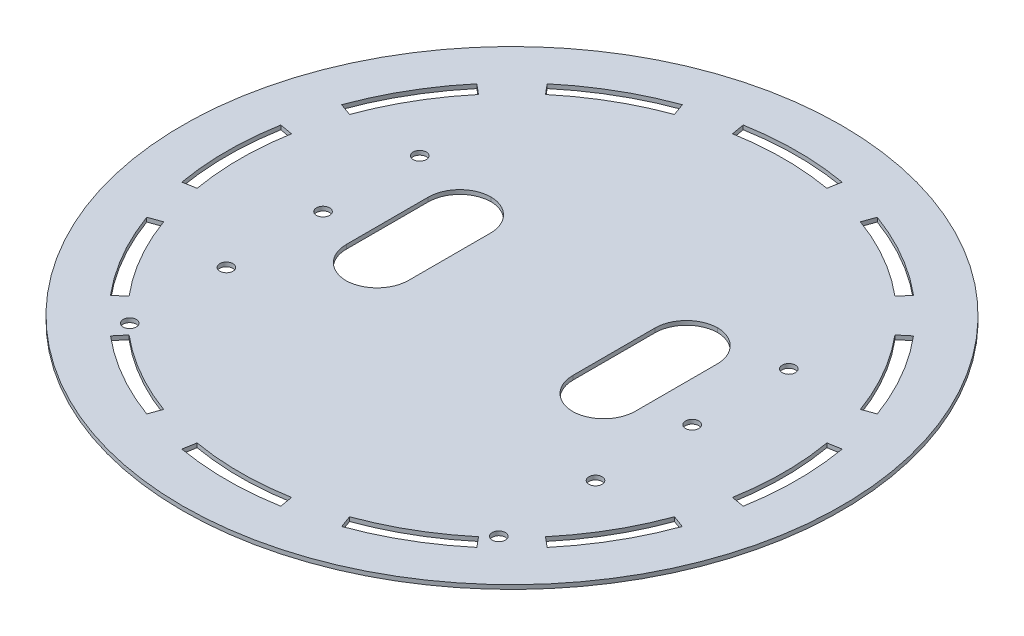
SolidWorks part; units mm, degrees
ref_plane "Front Plane" through (0, 0, 0) normal (0, 0, 1) x (1, 0, 0)
ref_plane "Top Plane" through (0, 0, 0) normal (0, 1, 0) x (1, 0, 0)
ref_plane "Right Plane" through (0, 0, 0) normal (1, 0, 0) x (0, 0, -1)
sketch "Sketch1" plane through (0, 0, 0) normal (0, 1, 0) x (1, 0, 0)
  line L0 (0, 0) -> (0, -79.375)
  line L1 (7.1438, -66.675) -> (-7.1437, -66.675)
  line L2 (50.8, 22.225) -> (76.2, 22.225)
  line L3 (-63.5, -47.625) -> (-50.8, -47.625)
  line L4 (-50.8, -47.625) -> (-50.8, 22.225)
  line L5 (63.5, -47.625) -> (50.8, -47.625)
  line L6 (50.8, -47.625) -> (50.8, 22.225)
  line L7 (-50.8, 22.225) -> (-76.2, 22.225)
  line L8 (0, 0) -> (-27.2811, 0)
  circle A0 centre (0, 0) radius 79.375
  circle A1 centre (-7.1437, -66.675) radius 1.5875
  circle A2 centre (7.1438, -66.675) radius 1.5875
  circle A3 centre (7.1438, 66.675) radius 1.5875
  circle A4 centre (-7.1437, 66.675) radius 1.5875
  point P7 (0, -66.675)
  dimension "D1" = 7.1437
  dimension "D3" = 50.8
  dimension "D6" = 3.175
  dimension "D2" = 12.7
  dimension "D4" = 69.85
  dimension "D5" = 47.625
extrude "Boss-Extrude5" add sketch "Sketch1" along normal blind 1.5875 contours A2 A0 L5 L6 L2 L7 L4 L3 A1 A3 region at (0, 0, -2.0947)
fillet "Fillet2" radius 2.54 1 edges at (-63.5, 0.7937, 47.625)
fillet "Fillet3" radius 2.54 1 edges at (63.5, 0.7937, 47.625)
fillet "Fillet4" radius 5.08 2 edges at (-76.2, 0.7937, -22.225) (76.2, 0.7937, -22.225)
sketch "Sketch2" plane through (0, 1.5875, 0) normal (0, 1, 0) x (1, 0, 0)
  line L0 (0, 0) -> (0, 79.375)
  line L1 (0, 0) -> (-67.0566, 0)
  line L2 (0, 0) -> (-61.0886, 27.6545)
  line L3 (0, 0) -> (-43.6778, 50.8806)
  line L4 (0, 0) -> (-63.2664, 22.225)
  line L5 (-50.8, 22.225) -> (-69.0955, 22.225) construction
  line L6 (0, 0) -> (0, 2.6153)
  line L7 (0, 0) -> (-39.0771, 54.4938)
  line L8 (0, 0) -> (-12.3858, 65.9028)
  line L9 (-62.5348, 28.3092) -> (-59.6424, 26.9998)
  line L10 (-43.6778, 50.8806) -> (-44.7118, 52.0852)
  line L11 (-43.6778, 50.8806) -> (-42.6438, 49.6761)
  line L12 (-39.0771, 54.4938) -> (-40.0022, 55.7839)
  line L13 (-39.0771, 54.4938) -> (-38.152, 53.2037)
  line L14 (-43.6778, 50.8806) -> (-42.6438, 49.6761)
  line L15 (-12.3858, 65.9028) -> (-12.0926, 64.3426)
  line L16 (-12.3858, 65.9028) -> (-12.679, 67.463)
  line L17 (61.5813, 22.225) -> (64.9466, 22.225)
  line L18 (50.8, 22.225) -> (69.0955, 22.225) construction
  line L19 (12.3858, 65.9028) -> (12.679, 67.463)
  line L20 (12.3858, 65.9028) -> (12.0926, 64.3426)
  line L21 (39.0771, 54.4938) -> (38.152, 53.2037)
  line L22 (43.6778, 50.8806) -> (42.6438, 49.6761)
  line L23 (39.0771, 54.4938) -> (40.0022, 55.7839)
  line L24 (43.6778, 50.8806) -> (42.6438, 49.6761)
  line L25 (43.6778, 50.8806) -> (44.7118, 52.0852)
  line L26 (62.5348, 28.3092) -> (59.6424, 26.9998)
  line L27 (-50.8, -41.2985) -> (-50.8, -43.7716)
  line L28 (-50.8, -47.625) -> (-50.8, 22.225) construction
  line L29 (50.8, -41.2985) -> (50.8, -46.1668)
  line L30 (50.8, -47.625) -> (50.8, 22.225) construction
  line L31 (39.0771, -54.4938) -> (40.0022, -55.7839)
  line L32 (39.0771, -54.4938) -> (38.152, -53.2037)
  line L33 (12.3858, -65.9028) -> (12.0926, -64.3426)
  line L34 (12.3858, -65.9028) -> (12.679, -67.463)
  line L35 (-12.3858, -65.9028) -> (-12.679, -67.463)
  line L36 (-12.3858, -65.9028) -> (-12.0926, -64.3426)
  line L37 (-39.0771, -54.4938) -> (-38.152, -53.2037)
  line L38 (-39.0771, -54.4938) -> (-40.0022, -55.7839)
  arc A0 (-63.2664, 22.225) -> (-50.8, -43.7716) centre (0, 0) ccw
  arc A1 (73.8199, 29.172) -> (-73.8199, 29.172) centre (0, 0) ccw construction
  circle A2 centre (-7.1437, 66.675) radius 2.3813
  circle A3 centre (7.1437, 66.675) radius 2.3813
  circle A4 centre (7.1437, -66.675) radius 2.3813
  circle A5 centre (-7.1437, -66.675) radius 2.3813
  arc A6 (12.679, -67.463) -> (40.0022, -55.7839) centre (0, 0) ccw
  arc A7 (-61.7686, 21.6988) -> (-50.8, -41.2985) centre (0, 0) ccw
  arc A8 (-44.7118, 52.0852) -> (-62.5348, 28.3092) centre (0, 0) ccw
  arc A9 (-42.6438, 49.6761) -> (-59.6424, 26.9998) centre (0, 0) ccw
  arc A10 (12.0926, 64.3426) -> (38.152, 53.2037) centre (0, 0) cw
  arc A11 (12.679, 67.463) -> (40.0022, 55.7839) centre (0, 0) cw
  arc A12 (42.6438, 49.6761) -> (59.6424, 26.9998) centre (0, 0) cw
  arc A13 (-12.679, 67.463) -> (-40.0022, 55.7839) centre (0, 0) ccw
  arc A14 (44.7118, 52.0852) -> (62.5348, 28.3092) centre (0, 0) cw
  arc A15 (-12.0926, 64.3426) -> (-38.152, 53.2037) centre (0, 0) ccw
  arc A16 (12.0926, -64.3426) -> (38.152, -53.2037) centre (0, 0) ccw
  arc A17 (-12.0926, -64.3426) -> (-38.152, -53.2037) centre (0, 0) cw
  arc A18 (50.8, -46.1668) -> (64.9466, 22.225) centre (0, 0) ccw
  arc A19 (50.8, -43.7716) -> (63.2664, 22.225) centre (0, 0) ccw
  arc A20 (50.8, -41.2985) -> (61.5813, 22.225) centre (0, 0) ccw
  arc A21 (-12.679, -67.463) -> (-40.0022, -55.7839) centre (0, 0) cw
  circle M13 centre (-7.1437, -66.675) radius 1.5875
  circle M14 centre (7.1438, -66.675) radius 1.5875
  circle M15 centre (7.1438, 66.675) radius 1.5875
  circle M16 centre (-7.1437, 66.675) radius 1.5875
  dimension "D2" = 4.7625
  dimension "D7" = 1.5875
  dimension "D8" = 3.175
  dimension "D1" = 5
  dimension "D3" = 25
  dimension "D4" = 5
  dimension "D5" = 25
extrude "Cut-Extrude1" cut sketch "Sketch2" against normal blind 2.54 contours A9 L3 L10 A8 L9 L2 | A15 L8 L16 A13 L12 L7 | A2 M16 | A3 M15 | A11 L19 L20 A10 L21 L23 | A14 L25 L22 A12 L26 | A21 L35 L36 A17 L37 L38 | A5 M13 | A4 M14 | A16 L33 L34 A6 L31 L32 region at (-53.2404, 1.5875, -39.9101) region at (-26.1525, 1.5875, -61.1833) region at (26.1525, 1.5875, -61.1833) region at (53.2404, 1.5875, -39.9101) region at (26.1525, 1.5875, 61.1833) region at (-26.1525, 1.5875, 61.1833) region at (-9.4576, 1.5875, -66.675) region at (4.8299, 1.5875, -66.675) region at (4.8299, 1.5875, 66.675) region at (-9.4576, 1.5875, 66.675)
sketch "Sketch3" plane through (0, 1.5875, 0) normal (0, 1, 0) x (1, 0, 0)
  line L0 (-50.8, 22.225) -> (-50.8, -47.625)
  line L1 (-50.8, -47.625) -> (-44.45, -47.625)
  line L2 (-50.8, 22.225) -> (-44.45, 22.225)
  line L3 (0, 0) -> (0, 32.9013)
  circle A0 centre (-44.45, -47.625) radius 1.5875
  circle A1 centre (-44.45, 22.225) radius 1.5875
  circle A2 centre (44.45, 22.225) radius 1.5875
  circle A3 centre (44.45, -47.625) radius 1.5875
  dimension "D2" = 3.175
  dimension "D4" = 3.175
  dimension "D1" = 6.35
  dimension "D3" = 6.35
extrude "Cut-Extrude2" cut sketch "Sketch3" against normal blind 2.54 contours A1 | A2 | A0 | A3 region at (-44.45, 1.5875, 46.0824) region at (-44.45, 1.5875, -23.7676) region at (44.45, 1.5875, -22.225) region at (44.45, 1.5875, 47.625)
sketch "Sketch4" plane through (0, 1.5875, 0) normal (0, 1, 0) x (1, 0, 0)
  line L0 (-44.45, -47.625) -> (-44.45, 22.225)
  line L1 (-44.45, 22.225) -> (-50.8, 22.225)
  line L2 (-50.8, -47.625) -> (-50.8, 22.225) construction
  line L3 (0, 0) -> (0, -67.5878)
  line L4 (44.45, -47.625) -> (44.45, 22.225)
  circle A0 centre (-44.45, 22.225) radius 1.5875
  circle A1 centre (-44.45, -12.7) radius 1.5875
  circle A2 centre (44.45, -12.7) radius 1.5875
  dimension "D2" = 3.175
  dimension "D1" = 69.85
extrude "Cut-Extrude3" cut sketch "Sketch4" against normal blind 2.54 contours L0 A1 | L0 A1 | A2 L4 | A2 L4 region at (-45.1238, 1.5875, 12.7) region at (-43.7762, 1.5875, 12.7) region at (43.7762, 1.5875, 12.7) region at (45.1238, 1.5875, 12.7)
sketch "Sketch5" plane through (0, 1.5875, 0) normal (0, 1, 0) x (1, 0, 0)
  line L0 (-50.8, -12.7) -> (-34.8, -12.7)
  line L1 (-50.8, -47.625) -> (-50.8, 22.225) construction
  line L2 (-50.8, 22.225) -> (-34.8, 22.225)
  line L3 (-34.8, 22.225) -> (-34.8, -12.7)
  line L4 (0, 0) -> (0, 64.5379)
  line L5 (-34.8, 22.225) -> (-19.8, 22.225)
  line L6 (-19.8, 22.225) -> (-19.8, -12.7)
  line L7 (-19.8, -12.7) -> (-34.8, -12.7)
  line L8 (19.8, -12.7) -> (34.8, -12.7)
  line L9 (19.8, 22.225) -> (19.8, -12.7)
  line L10 (34.8, 22.225) -> (19.8, 22.225)
  line L11 (34.8, 22.225) -> (34.8, -12.7)
  dimension "D1" = 16
  dimension "D2" = 16
extrude "Cut-Extrude4" cut sketch "Sketch5" against normal through all contours L7 L6 L5 L3 | L11 L10 L9 L8 region at (-27.3, 1.5875, -4.7625) region at (27.3, 1.5875, -4.7625)
fillet "Fillet5" radius 7.62 4 edges at (-19.8, 0.7937, 12.7) (-34.8, 0.7937, 12.7) (-19.8, 0.7937, -22.225) (-34.8, 0.7937, -22.225)
fillet "Fillet6" radius 7.62 4 edges at (34.8, 0.7937, 12.7) (34.8, 0.7937, -22.225) (19.8, 0.7937, -22.225) (19.8, 0.7937, 12.7)
sketch "Sketch6" plane through (0, 1.5875, 0) normal (0, 1, 0) x (1, 0, 0)
  line L0 (-50.8, 22.225) -> (-69.0955, 22.225)
  line L1 (-69.0955, 22.225) -> (-69.0955, 39.0667)
  line L2 (-50.8, 22.225) -> (-50.8, -60.9898)
  line L3 (50.8, 22.225) -> (69.0955, 22.225)
  line L4 (69.0955, 22.225) -> (69.0955, 39.0667)
  line L5 (50.8, 22.225) -> (50.8, -60.9898)
  circle A0 centre (0, 0) radius 79.375
extrude "Boss-Extrude6" add sketch "Sketch6" against normal blind 1.5875 contours L1 A0 L2 L0 | L5 A0 L4 L3 region at (-63.4454, 1.5875, 10.5781) region at (63.4454, 1.5875, 10.5781)
sketch "Sketch7" plane through (0, 0, 0) normal (0, -1, 0) x (1, 0, 0)
  circle A0 centre (0, 0) radius 79.375
extrude "Cut-Extrude5" cut sketch "Sketch7" against normal blind 0.5875
sketch "Sketch8" plane through (0, 1.5875, 0) normal (0, 1, 0) x (1, 0, 0)
  circle A0 centre (-44.45, -12.7) radius 1.5875
  circle A1 centre (44.45, -12.7) radius 1.5875
  circle A2 centre (-7.1437, -66.675) radius 2.3813
  circle A3 centre (7.1437, -66.675) radius 2.3812
  circle A4 centre (-7.1437, 66.675) radius 2.3812
  circle A5 centre (7.1437, 66.675) radius 2.3813
extrude "Boss-Extrude7" add sketch "Sketch8" against normal up to surface (1 mm away) up to face at (-53.0191, 0.5875, -39.7442)
sketch "Sketch9" plane through (0, 1.5875, 0) normal (0, 1, 0) x (1, 0, 0)
  line L0 (-44.45, 22.225) -> (-44.45, -1.0583)
  line L1 (-44.45, -1.0583) -> (-44.45, -24.3417)
  line L2 (0, 0) -> (0, 22.225)
  circle A0 centre (-44.45, -1.0583) radius 1.5875
  circle A1 centre (-44.45, -24.3417) radius 1.5875
  circle A2 centre (44.45, -24.3417) radius 1.5875
  circle A3 centre (44.45, -1.0583) radius 1.5875
  dimension "D2" = 23.2833
  dimension "D3" = 3.175
  dimension "D4" = 3.175
  dimension "D1" = 23.2833
extrude "Cut-Extrude7" cut sketch "Sketch9" against normal blind 2.54 contours A1 | L0 A0 L1 | L1 A0 L0 | A2 | A3 region at (-43.7762, 1.5875, 1.0583) region at (-43.3592, 1.5875, 23.2509) region at (-45.1238, 1.5875, 1.0583) region at (44.45, 1.5875, 24.3417) region at (44.45, 1.5875, 1.0583)
sketch "Sketch10" plane through (0, 1.5875, 0) normal (0, 1, 0) x (1, 0, 0)
  line L0 (-65.4691, 0) -> (-68.6441, 0)
  line L1 (65.4691, 0) -> (68.6441, 0)
  circle A0 centre (0, 0) radius 68.6441
  circle A1 centre (0, 0) radius 65.4691
  line M21 (12.0926, 64.3426) -> (12.679, 67.463)
  arc M22 (12.679, 67.463) -> (40.0022, 55.7839) centre (0, 0) cw
  line M23 (40.0022, 55.7839) -> (38.152, 53.2037)
  arc M24 (38.152, 53.2037) -> (12.0926, 64.3426) centre (0, 0) ccw
  line M25 (-12.679, 67.463) -> (-12.0926, 64.3426)
  arc M26 (-12.0926, 64.3426) -> (-38.152, 53.2037) centre (0, 0) ccw
  line M27 (-38.152, 53.2037) -> (-40.0022, 55.7839)
  arc M28 (-40.0022, 55.7839) -> (-12.679, 67.463) centre (0, 0) cw
  line M29 (-44.7118, 52.0852) -> (-42.6438, 49.6761)
  arc M30 (-42.6438, 49.6761) -> (-59.6424, 26.9998) centre (0, 0) ccw
  line M31 (-59.6424, 26.9998) -> (-62.5348, 28.3092)
  arc M32 (-62.5348, 28.3092) -> (-44.7118, 52.0852) centre (0, 0) cw
  line M33 (42.6438, 49.6761) -> (44.7118, 52.0852)
  arc M34 (44.7118, 52.0852) -> (62.5348, 28.3092) centre (0, 0) cw
  line M35 (62.5348, 28.3092) -> (59.6424, 26.9998)
  arc M36 (59.6424, 26.9998) -> (42.6438, 49.6761) centre (0, 0) ccw
extrude "Boss-Extrude8" add sketch "Sketch10" against normal up to surface (1 mm away) contours M29 M32 M31 M30 | M25 M28 M27 M26 | M21 M24 M23 M22 | M33 M36 M35 M34 region at (-53.2404, 1.5875, -39.9101) region at (53.2404, 1.5875, -39.9101) region at (-26.1525, 1.5875, -61.1833) region at (26.1525, 1.5875, -61.1833) up to face at (44.45, 0.5875, 22.7542)
sketch "Sketch11" plane through (0, 1.5875, 0) normal (0, 1, 0) x (1, 0, 0)
  line L0 (0, 0) -> (-68.6441, 0)
  line L1 (0, 0) -> (-67.6013, 11.9199)
  line L2 (0, 0) -> (-67.6013, -11.9199)
  line L3 (0, 0) -> (-56.1266, 56.1266)
  line L4 (0, 0) -> (-11.9199, 67.6013)
  line L5 (0, 0) -> (11.9199, 67.6013)
  line L6 (0, 0) -> (56.1266, -56.1266)
  line L7 (0, 0) -> (56.1266, 56.1266)
  line L8 (0, 0) -> (67.6013, 11.9199)
  line L9 (0, 0) -> (67.6013, -11.9199)
  line L10 (0, 0) -> (11.9199, -67.6013)
  line L11 (0, 0) -> (-11.9199, -67.6013)
  line L12 (0, 0) -> (-39.3726, 56.23)
  line L13 (0, 0) -> (-56.23, 39.3726)
  line L14 (0, 0) -> (0, 37.7088)
  line L15 (0, 0) -> (39.3726, 56.23)
  line L16 (0, 0) -> (56.23, 39.3726)
  circle A0 centre (0, 0) radius 68.6441
  circle A1 centre (0, 0) radius 65.4691
  circle A3 centre (0, 0) radius 79.375
  dimension "D3" = 158.75
  dimension "D1" = 10
  dimension "D2" = 10
  dimension "D4" = 45
  dimension "D5" = 20
  dimension "D6" = 180
  dimension "D7" = 90
  dimension "D8" = 35
  dimension "D9" = 10
  dimension "D10" = 10
extrude "Cut-Extrude9" cut sketch "Sketch11" against normal blind 2.54 contours A1 L11 A0 L10 | A1 L5 A0 L4 | A1 L12 A0 L3 | A1 L3 A0 L13 | A1 L1 A0 L0 | A1 L0 A0 L2 | A1 L9 A0 L8 | A1 L16 A0 L7 | A1 L7 A0 L15 region at (-66.7291, 1.5875, 5.838) region at (-66.7291, 1.5875, -5.838) region at (-51.3128, 1.5875, -43.0565) region at (-43.0565, 1.5875, -51.3128) region at (0, 1.5875, -66.7291) region at (43.0565, 1.5875, -51.3128) region at (51.3128, 1.5875, -43.0565) region at (66.7291, 1.5875, 0) region at (0, 1.5875, 66.7291)
sketch "Sketch12" plane through (0, 1.5875, 0) normal (0, 1, 0) x (1, 0, 0)
  line L0 (0, 0) -> (-40.0022, -55.7839)
  line L1 (0, 0) -> (-18.5106, -66.1012)
  line L2 (0, 0) -> (0, -68.6441)
  line L3 (0, 0) -> (18.5106, -66.1012)
  line L4 (0, 0) -> (40.0022, -55.7839)
  line L5 (-12.0926, -64.3426) -> (-12.679, -67.463)
  line L6 (12.0926, -64.3426) -> (12.679, -67.463)
  circle A0 centre (0, 0) radius 68.6441
  circle A1 centre (0, 0) radius 65.4691
  dimension "D1" = 20
extrude "Boss-Extrude9" add sketch "Sketch12" against normal up to surface (1 mm away) contours A1 L1 A0 L5 | A1 L6 A0 L3 region at (-15.2467, 1.5875, 65.2913) region at (15.2467, 1.5875, 65.2913) up to face at (66.5472, 0.5875, 0)
sketch "Sketch13" plane through (0, 1.5875, 0) normal (0, 1, 0) x (1, 0, 0)
  line L0 (0, 0) -> (-67.6013, 11.9199)
  line L1 (0, 0) -> (-11.9199, 67.6013)
  line L2 (0, 0) -> (-64.5044, 23.4777)
  line L3 (0, 0) -> (-52.5844, 44.1236)
  line L4 (0, 0) -> (-44.1236, 52.5844)
  line L5 (0, 0) -> (-23.4777, 64.5044)
  line L6 (0, 0) -> (0, 68.6441)
  line L7 (0, 0) -> (23.4777, 64.5044)
  line L8 (0, 0) -> (44.1236, 52.5844)
  line L9 (0, 0) -> (52.5844, 44.1236)
  line L10 (0, 0) -> (64.5044, 23.4777)
  line L11 (0, 0) -> (-68.6441, 0)
  line L12 (0, 0) -> (64.5044, -23.4777)
  line L13 (0, 0) -> (52.5844, -44.1236)
  line L14 (0, 0) -> (-52.5844, -44.1236)
  line L15 (0, 0) -> (-64.5044, -23.4777)
  circle A1 centre (0, 0) radius 68.6441
  circle A2 centre (0, 0) radius 65.4691
  dimension "D1" = 70
  dimension "D2" = 10
  dimension "D3" = 20
  dimension "D4" = 10
  dimension "D5" = 20
  dimension "D6" = 10
  dimension "D7" = 90
extrude "Cut-Extrude10" cut sketch "Sketch13" against normal blind 2.54 contours A2 L15 A1 L14 | A2 L13 A1 L12 | A2 L10 A1 L9 | A2 L8 A1 L7 | A2 L5 A1 L4 | A2 L3 A1 L2 region at (-57.7891, 1.5875, -33.3646) region at (-33.3646, 1.5875, -57.7891) region at (33.3646, 1.5875, -57.7891) region at (57.7891, 1.5875, -33.3646) region at (57.7891, 1.5875, 33.3646) region at (-57.7891, 1.5875, 33.3646)
sketch "Sketch15" plane through (0, 1.5875, 0) normal (0, 1, 0) x (1, 0, 0)
  line L0 (0, 0) -> (-64.5044, 23.4777)
  line L1 (0, 0) -> (-52.5844, 44.1236)
  line L2 (0, 0) -> (-44.1236, 52.5844)
  line L3 (0, 0) -> (0, 68.6441)
  line L4 (0, 0) -> (44.1236, 52.5844)
  line L5 (0, 0) -> (52.5844, 44.1236)
  circle A0 centre (0, 0) radius 68.6441
  circle A1 centre (0, 0) radius 65.4691
  dimension "D1" = 20
  dimension "D2" = 10
extrude "Boss-Extrude10" add sketch "Sketch15" against normal up to surface (1 mm away) contours A1 L2 A0 L1 | A1 L5 A0 L4 region at (-47.3649, 1.5875, -47.3649) region at (47.3649, 1.5875, -47.3649) up to face at (-57.6316, 0.5875, 33.2736)
sketch "Sketch16" plane through (0, 1.5875, 0) normal (0, 1, 0) x (1, 0, 0)
  line L0 (0, 0) -> (-11.9199, -67.6013)
  line L1 (0, 0) -> (-23.4777, -64.5044)
  line L2 (0, 0) -> (-44.1236, -52.5844)
  line L3 (0, 0) -> (0, -68.6441)
  line L4 (0, 0) -> (23.4777, -64.5044)
  line L5 (0, 0) -> (44.1236, -52.5844)
  circle A0 centre (0, 0) radius 68.6441
  circle A1 centre (0, 0) radius 65.4691
  dimension "D1" = 10
  dimension "D2" = 20
extrude "Cut-Extrude11" cut sketch "Sketch16" against normal blind 2.54 contours A1 L2 A0 L1 | A1 L4 A0 L5 region at (-33.3646, 1.5875, 57.7891) region at (33.3646, 1.5875, 57.7891)
sketch "Sketch17" plane through (0, 1.5875, 0) normal (0, 1, 0) x (1, 0, 0)
  line L0 (0, 0) -> (0, -68.6441)
  line L1 (0, 0) -> (-11.9199, -67.6013)
  line L2 (0, 0) -> (-23.4777, -64.5044)
  line L3 (0, 0) -> (11.9199, -67.6013)
  line L4 (0, 0) -> (23.4777, -64.5044)
  arc A0 (-11.9199, -67.6013) -> (11.9199, -67.6013) centre (0, 0) ccw construction
  circle A1 centre (0, 0) radius 68.6441
  circle A2 centre (0, 0) radius 65.4691
  dimension "D1" = 10
extrude "Boss-Extrude11" add sketch "Sketch17" against normal up to surface (1 mm away) contours A2 L2 A1 L1 | A2 L3 A1 L4 region at (-17.3367, 1.5875, 64.7016) region at (17.3367, 1.5875, 64.7016) up to face at (-30.945, 0.5875, 58.6377)
